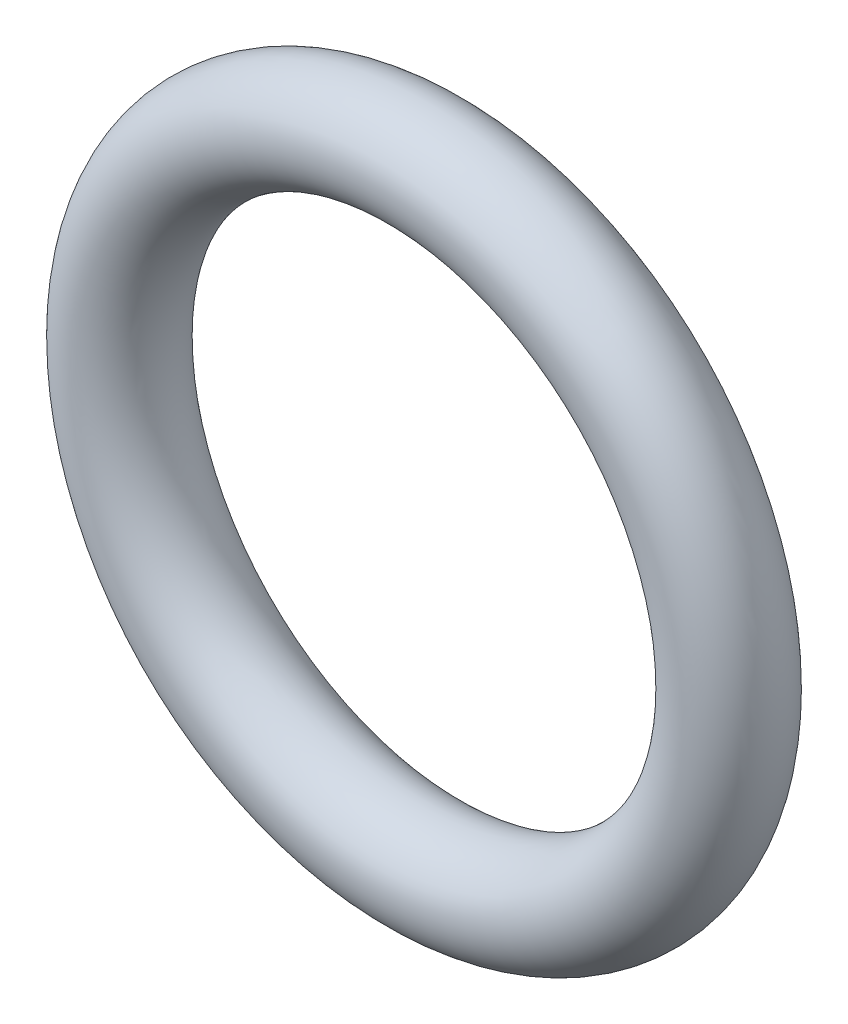
SolidWorks part; units mm, degrees
ref_plane "Front" through (0, 0, 0) normal (0, 0, 1) x (1, 0, 0)
ref_plane "Top" through (0, 0, 0) normal (0, 1, 0) x (1, 0, 0)
ref_plane "Right" through (0, 0, 0) normal (1, 0, 0) x (0, 0, -1)
sketch "Sketch1" plane through (0, 0, 0) normal (0, 0, 1) x (1, 0, 0)
  circle A0 centre (0, 0) radius 5.9
  dimension "d1" = 11.8
sketch "Sketch2" plane through (0, 0, 0) normal (0, 1, 0) x (1, 0, 0)
  circle A0 centre (-7.1, 0) radius 1.2
  point P2 (-5.9, 0)
  dimension "d2" = 2.4
sweep "Sweep1" add profiles "Sketch2" path "Sketch1"
ref_axis "Axis1" through (0, 0, -5.0798) along (0, 0, 1)
